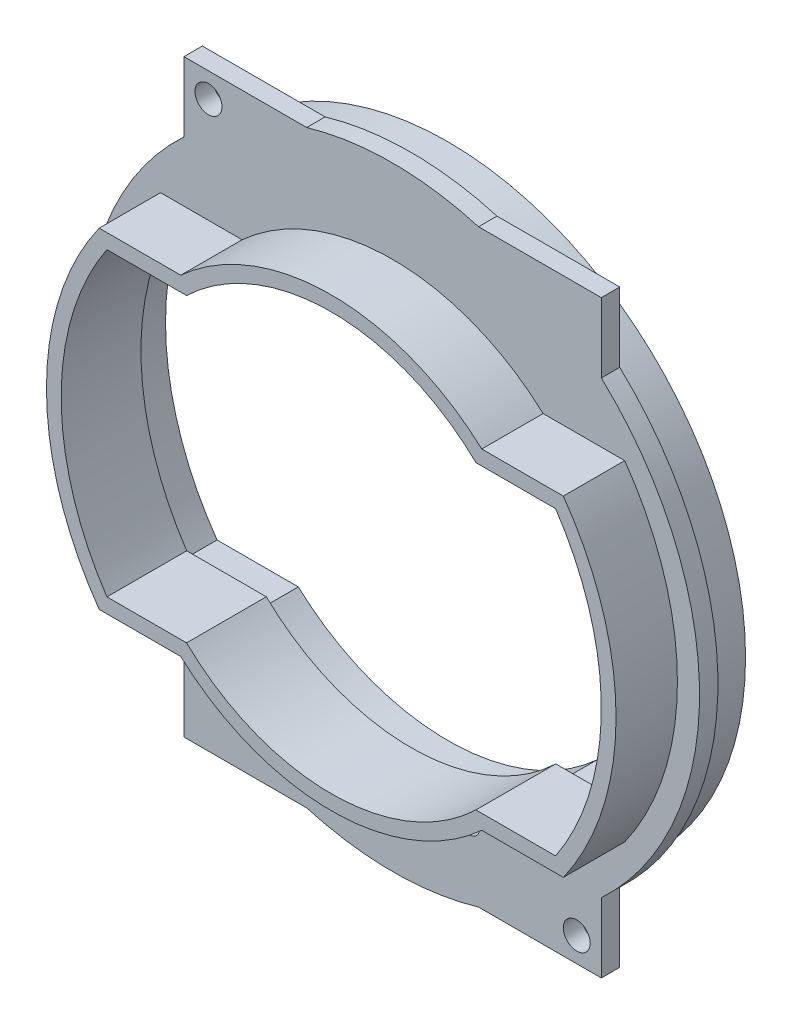
SolidWorks part; units mm, degrees
ref_plane "前视基准面" through (0, 0, 0) normal (0, 0, 1) x (1, 0, 0)
ref_plane "上视基准面" through (0, 0, 0) normal (0, 1, 0) x (1, 0, 0)
ref_plane "右视基准面" through (0, 0, 0) normal (1, 0, 0) x (0, 0, -1)
other "Configuration Table"
sketch "草图1" plane through (0, 0, 0) normal (0, 0, 1) x (1, 0, 0)
  line L0 (18.274, 12.25) -> (-18.274, 12.25)
  line L1 (-18.274, -12.25) -> (18.274, -12.25)
  line L2 (-26.9084, 0) -> (29.3247, 0) construction
  circle A0 centre (0, 0) radius 17
  circle A1 centre (0, 0) radius 22
  circle A2 centre (0, 0) radius 25
  dimension "D1" = 34
  dimension "D2" = 44
  dimension "D4" = 50
  dimension "D3" = 24.5
extrude "凸台-拉伸1" add sketch "草图1" along normal blind 1.5 contours A2 L2 A1 | L2 A2 A1 | L1 A1 A0 | L0 A1 A0 region at (0, 22.559, 0) region at (0, 17.1494, 0) region at (23.5, -0.559, 0) region at (0, -17.1494, 0)
sketch "草图2" plane through (0, 0, 1.5) normal (0, 0, 1) x (1, 0, 0)
  line L0 (-18.274, 12.25) -> (-11.7872, 12.25)
  line L1 (11.7872, 12.25) -> (18.274, 12.25)
  line L2 (11.7872, -12.25) -> (18.274, -12.25)
  line L3 (-18.274, -12.25) -> (-11.7872, -12.25)
  line L4 (-18.9034, 13.45) -> (-12.2612, 13.45)
  line L5 (12.2612, 13.45) -> (18.9034, 13.45)
  line L6 (12.2612, -13.45) -> (18.9034, -13.45)
  line L7 (-18.9034, -13.45) -> (-12.2612, -13.45)
  arc A0 (18.274, 12.25) -> (18.274, -12.25) centre (0, 0) cw
  arc A1 (11.7872, -12.25) -> (-11.7872, -12.25) centre (0, 0) cw
  arc A2 (-11.7872, 12.25) -> (11.7872, 12.25) centre (0, 0) cw
  arc A3 (-18.274, -12.25) -> (-18.274, 12.25) centre (0, 0) cw
  arc A4 (-12.2612, 13.45) -> (12.2612, 13.45) centre (0, 0) cw
  arc A5 (18.9034, 13.45) -> (18.9034, -13.45) centre (0, 0) cw
  arc A6 (12.2612, -13.45) -> (-12.2612, -13.45) centre (0, 0) cw
  arc A7 (-18.9034, -13.45) -> (-18.9034, 13.45) centre (0, 0) cw
  dimension "D1" = 1.2
extrude "凸台-拉伸2" add sketch "草图2" along normal blind 5
sketch "草图5" plane through (0, 0, 0) normal (0, 0, -1) x (-1, 0, 0)
  line L40 (-18.7999, -13.25) -> (-12.1835, -13.25)
  line L41 (12.1835, -13.25) -> (18.7999, -13.25)
  line L42 (18.7999, 13.25) -> (12.1835, 13.25)
  line L43 (-12.1835, 13.25) -> (-18.7999, 13.25)
  line L44 (-18.7999, -13.25) -> (-12.1835, -13.25)
  line L45 (12.1835, -13.25) -> (18.7999, -13.25)
  line L46 (18.7999, 13.25) -> (12.1835, 13.25)
  line L47 (-12.1835, 13.25) -> (-18.7999, 13.25)
  circle A37 centre (0, 0) radius 24.25
  arc A41 (-18.7999, 13.25) -> (-18.7999, -13.25) centre (0, 0) ccw
  arc A42 (-12.1835, -13.25) -> (12.1835, -13.25) centre (0, 0) ccw
  arc A43 (18.7999, -13.25) -> (18.7999, 13.25) centre (0, 0) ccw
  arc A44 (12.1835, 13.25) -> (-12.1835, 13.25) centre (0, 0) ccw
  arc A45 (-18.7999, 13.25) -> (-18.7999, -13.25) centre (0, 0) ccw
  arc A46 (-12.1835, -13.25) -> (12.1835, -13.25) centre (0, 0) ccw
  arc A47 (18.7999, -13.25) -> (18.7999, 13.25) centre (0, 0) ccw
  arc A48 (12.1835, 13.25) -> (-12.1835, 13.25) centre (0, 0) ccw
  dimension "D2" = 48.5
  dimension "D1" = 1
extrude "凸台-拉伸4" add sketch "草图5" along normal blind 3
sketch "草图6" plane through (0, 0, 0) normal (0, 0, 1) x (1, 0, 0)
  line L1 (-17, -24) -> (17, -24)
  line L2 (-17, -24) -> (-17, 24)
  line L3 (-17, 24) -> (17, 24)
  line L4 (17, -24) -> (17, 24)
  line L5 (-17, -24) -> (17, 24) construction
  line L6 (-17, 24) -> (17, -24) construction
  circle A2 centre (0, 0) radius 24
  point P0 (0, 0)
  dimension "D1" = 34
  dimension "D2" = 48
extrude "凸台-拉伸5" add sketch "草图6" along normal blind 1.5 contours A2 L3 L2 | A2 L4 L3 | A2 L1 L4 | A2 L2 L1 region at (-12.8852, -21.949, 0) region at (12.8852, -21.949, 0) region at (-12.8852, 21.949, 0) region at (12.8852, 21.949, 0)
sketch "草图7" plane through (0, 0, -3) normal (0, 0, -1) x (-1, 0, 0)
  line L0 (-12.8572, -14.6609) -> (0, 0) construction
  line L1 (0, 0) -> (0, -19.5) construction
  line L2 (0, 0) -> (-12.8572, -14.6609) construction
  line L3 (0, 0) -> (-10.8336, -16.2137) construction
  circle A0 centre (0, 0) radius 19.5 construction
  circle A1 centre (-12.8572, -14.6609) radius 0.5
  circle A2 centre (-10.8336, -16.2137) radius 0.5
  circle A3 centre (-8.6246, -17.489) radius 0.5
  circle A4 centre (-6.2681, -18.4651) radius 0.5
  circle A5 centre (-3.8043, -19.1253) radius 0.5
  circle A6 centre (-1.2754, -19.4582) radius 0.5
  circle A7 centre (1.2754, -19.4582) radius 0.5
  circle A8 centre (3.8043, -19.1253) radius 0.5
  circle A9 centre (6.2681, -18.4651) radius 0.5
  circle A10 centre (8.6246, -17.489) radius 0.5
  dimension "D1" = 39
  dimension "D2" = 1
  dimension "D3" = 41.25
  dimension "D5" = 7.5
  dimension "D4" = 10
extrude "切除-拉伸2" cut sketch "草图7" against normal through all
sketch "草图8" plane through (0, 0, 1.5) normal (0, 0, 1) x (1, 0, 0)
  line L0 (0, 0) -> (12.8572, -14.6609) construction
  line L1 (0, 0) -> (10.8336, -16.2137) construction
  circle A0 centre (12.8572, -14.6609) radius 0.8
  circle A1 centre (10.8336, -16.2137) radius 0.8
  circle A2 centre (8.6246, -17.489) radius 0.8
  circle A3 centre (6.2681, -18.4651) radius 0.8
  circle A4 centre (3.8043, -19.1253) radius 0.8
  circle A5 centre (1.2754, -19.4582) radius 0.8
  circle A6 centre (-1.2754, -19.4582) radius 0.8
  circle A7 centre (-3.8043, -19.1253) radius 0.8
  circle A8 centre (-6.2681, -18.4651) radius 0.8
  circle A9 centre (-8.6246, -17.489) radius 0.8
  dimension "D1" = 1.6
  dimension "D3" = 7.5
  dimension "D2" = 10
extrude "切除-拉伸3" cut sketch "草图8" against normal blind 4
sketch "草图9" plane through (0, 0, 1.5) normal (0, 0, 1) x (1, 0, 0)
  line L0 (-17, 24) -> (-7, 24) construction
  line L1 (-17, 18.3303) -> (-17, 24) construction
  line L2 (17, -24) -> (17, -18.3303) construction
  line L3 (7, -24) -> (17, -24) construction
  circle A0 centre (-15, 22) radius 1.1
  circle A1 centre (15, -22) radius 1.1
  dimension "D1" = 2.2
  dimension "D2" = 2
  dimension "D3" = 2
  dimension "D4" = 2
  dimension "D5" = 2
extrude "切除-拉伸4" cut sketch "草图9" against normal blind 10
